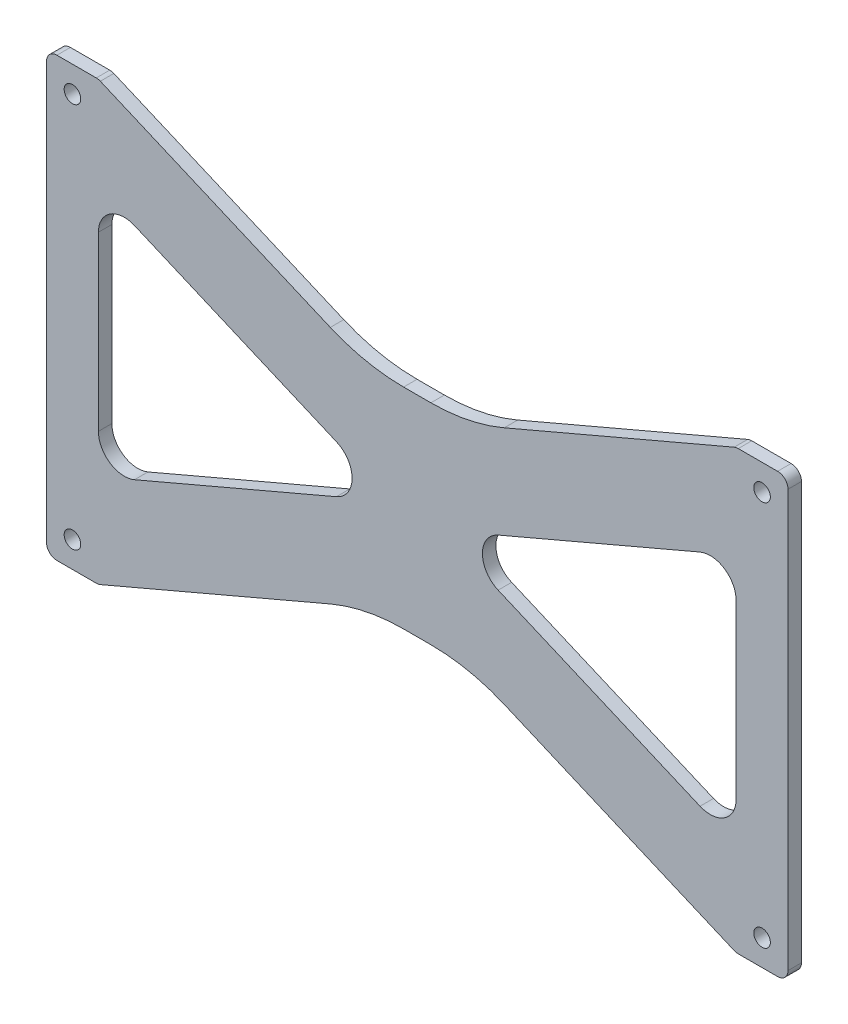
SolidWorks part; units mm, degrees
ref_plane "Front Plane" through (0, 0, 0) normal (0, 0, 1) x (1, 0, 0)
ref_plane "Top Plane" through (0, 0, 0) normal (0, 1, 0) x (1, 0, 0)
ref_plane "Right Plane" through (0, 0, 0) normal (1, 0, 0) x (0, 0, -1)
sketch "Sketch1" plane through (0, 0, 0) normal (0, 0, 1) x (1, 0, 0)
  line L0 (0, 85.9483) -> (0, -68.1569) construction
  line L1 (0, 65.8745) -> (-90.805, 65.8745) construction
  line L2 (-90.805, 65.8745) -> (-90.805, -41.3135)
  line L3 (-90.805, -41.3135) -> (0, -41.3135) construction
  line L4 (-90.805, -41.3135) -> (-78.105, -41.3135)
  line L5 (-90.805, 65.8745) -> (-78.105, 65.8745)
  line L6 (-90.805, 12.2805) -> (112.395, 12.2805) construction
  line L7 (90.805, -41.3135) -> (78.105, -41.3135)
  line L8 (90.805, 65.8745) -> (90.805, -41.3135)
  line L9 (90.805, 65.8745) -> (78.105, 65.8745)
  line L10 (-78.105, -41.3135) -> (-12.7, -13.3807)
  line L11 (-12.7, -13.3807) -> (12.7, -13.3807)
  line L12 (-12.7, 37.9418) -> (12.7, 37.9418)
  line L13 (-78.105, 65.8745) -> (-12.7, 37.9418)
  line L14 (78.105, -41.3135) -> (12.7, -13.3807)
  line L15 (78.105, 65.8745) -> (12.7, 37.9418)
  circle A0 centre (-84.455, 59.5245) radius 2.032
  circle A2 centre (-84.455, -34.9635) radius 2.032
  circle A7 centre (84.455, -34.9635) radius 2.032
  circle A8 centre (84.455, 59.5245) radius 2.032
  point P23 (0, -13.3807)
  point P29 (0, 37.9418)
  dimension "D3" = 4.064
  dimension "D1" = 90.805
  dimension "D2" = 6.35
  dimension "D4" = 6.35
  dimension "D5" = 94.488
  dimension "D6" = 6.35
  dimension "D7" = 107.188
  dimension "D8" = 12.7
  dimension "D9" = 12.7
  dimension "D10" = 71.12
  dimension "D11" = 12.2805
extrude "Boss-Extrude1" add sketch "Sketch1" along normal blind 3.302
fillet "Fillet1" radius 45.72 4 edges at (12.7, 37.9418, 1.651) (-12.7, 37.9418, 1.651) (12.7, -13.3807, 1.651) (-12.7, -13.3807, 1.651)
fillet "Fillet2" radius 2.54 8 edges at (-78.105, 65.8745, 1.651) (78.105, 65.8745, 1.651) (-78.105, -41.3135, 1.651) (78.105, -41.3135, 1.651) (90.805, -41.3135, 1.651) (90.805, 65.8745, 1.651) (-90.805, 65.8745, 1.651) (-90.805, -41.3135, 1.651)
sketch "Sketch2" plane through (0, 0, 3.302) normal (0, 0, 1) x (1, 0, 0)
  line L0 (-90.805, 12.2805) -> (90.805, 12.2805) construction
  line L3 (-90.805, 63.3345) -> (-90.805, -38.7735) construction
  line L4 (90.805, -38.7735) -> (90.805, 63.3345) construction
  line L5 (-78.105, 43.0145) -> (-78.105, -18.4535)
  line L6 (-88.265, -41.3135) -> (-78.6247, -41.3135) construction
  line L7 (-78.105, -18.4535) -> (-6.1409, 12.2805)
  line L8 (-77.6271, -41.1094) -> (-21.3026, -17.0546) construction
  line L9 (-78.105, 43.0145) -> (-6.1409, 12.2805)
  line L10 (0, -29.0797) -> (0, 60.2744) construction
  line L11 (78.105, 43.0145) -> (78.105, -18.4535)
  line L12 (78.105, -18.4535) -> (6.1409, 12.2805)
  line L13 (78.105, 43.0145) -> (6.1409, 12.2805)
  point P16 (-78.105, 12.2805)
  dimension "D1" = 22.86
  dimension "D2" = 12.7
extrude "Cut-Extrude1" cut sketch "Sketch2" against normal through all
fillet "Fillet3" radius 6.35 6 edges at (78.105, -18.4535, 1.651) (78.105, 43.0145, 1.651) (6.1409, 12.2805, 1.651) (-6.1409, 12.2805, 1.651) (-78.105, 43.0145, 1.651) (-78.105, -18.4535, 1.651)
